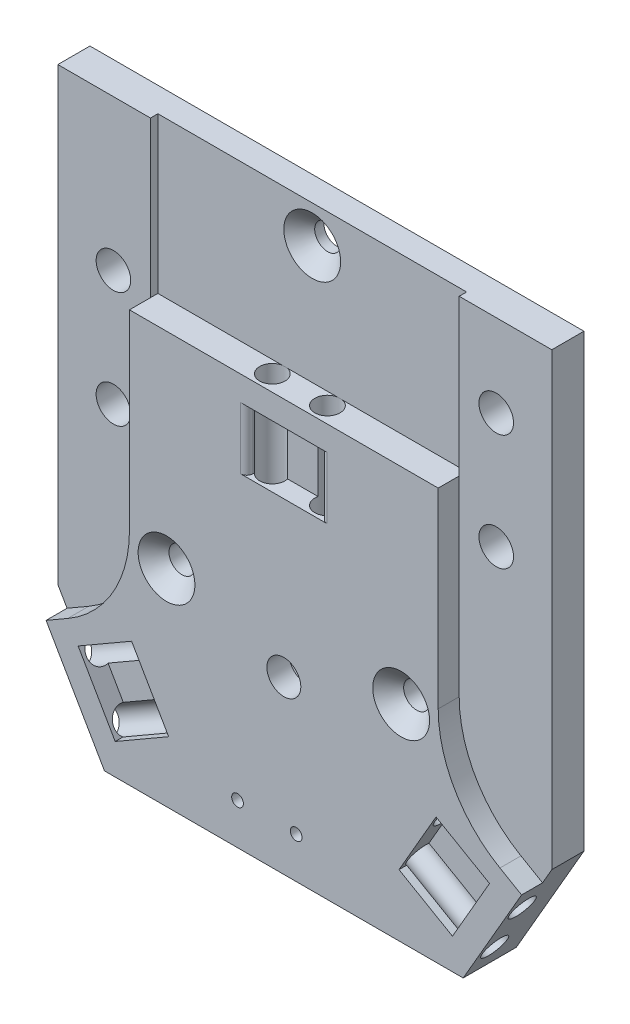
SolidWorks part; units mm, degrees
other "carriage coupler plate"
material "PET"
ref_plane "Front" through (0, 0, 0) normal (0, 0, 1) x (1, 0, 0)
ref_plane "Top" through (0, 0, 0) normal (0, 1, 0) x (1, 0, 0)
ref_plane "Right" through (0, 0, 0) normal (1, 0, 0) x (0, 0, -1)
sketch "Sketch1" plane through (0, 0, 0) normal (0, 0, 1) x (1, 0, 0)
  line L0 (0, 0) -> (0, 30) construction
  line L1 (0, 0) -> (25.9808, -15) construction
  line L2 (0, 0) -> (-25.9808, -15) construction
  dimension "D1" = 120
  dimension "D2" = 120
  dimension "D3" = 30
ref_plane "Plane1" through (0, 30, 0) normal (0, 1, 0) x (1, 0, 0)
sketch "Sketch2" plane through (0, 30, 0) normal (0, 1, 0) x (1, 0, 0)
  line L0 (-4.4589, 0) -> (0, -4.0148) construction
  line L1 (0, 0) -> (-25.9808, 0) construction
  line L2 (0, 0) -> (0, -4.0148) construction
  line L3 (-4.4589, 0) -> (0, 0) construction
  line L4 (0, -5.3962) -> (0, -4.0148) construction
  line L5 (0, -5.3962) -> (-4.4589, 0) construction
  line L7 (-4, -4.0148) -> (4, -4.0148) construction
  line L8 (3.9519, -3.3962) -> (-3.9519, -3.3962) construction
  line L9 (0, -0.3962) -> (0, -3.3962) construction
  line L10 (0, -4.0148) -> (0, -7.3926) construction
  circle A0 centre (-4.4589, 0) radius 2
  circle A1 centre (4.4589, 0) radius 2
  circle A2 centre (0, -4.0148) radius 4
  circle A3 centre (0, -5.3962) radius 5 construction
  circle A4 centre (0, -7.3926) radius 1.5
  dimension "D1" = 4
  dimension "D2" = 8
  dimension "D4" = 10
  dimension "D9" = 3
  dimension "D6" = 7.3926
  dimension "D8" = 8.9177
  dimension "D3" = 42
  dimension "D5" = 50.433
  dimension "D7" = 3.3962
  dimension "D10" = 0.6186
sketch "Sketch3" plane through (0, 0, 0) normal (0, 0, 1) x (1, 0, 0)
  line L0 (0, 30) -> (0, 35) construction
  line L2 (0, 35) -> (0, 39) construction
  line L3 (-25, 39) -> (25, 39)
  line L4 (25, 39) -> (25, -3.5116)
  line L5 (25, -3.5116) -> (38.5044, -11.3084)
  line L6 (0, 0) -> (0, 30) construction
  line L7 (-25, -3.5116) -> (-38.5044, -11.3084)
  line L8 (-25, 39) -> (-25, -3.5116)
  line L9 (4.4589, 30) -> (4.4589, 39) construction
  line L10 (25.9808, -15) -> (33.775, -19.5) construction
  line L11 (29.0456, -27.6916) -> (-29.0456, -27.6916)
  line L13 (0, 0) -> (25.9808, -15) construction
  line L14 (33.775, -19.5) -> (38.5044, -11.3084)
  line L15 (4.4589, 30) -> (0, 30) construction
  line L16 (4.4589, 30) -> (9.4589, 30) construction
  line L17 (-33.775, -19.5) -> (-38.5044, -11.3084)
  line L18 (33.775, -19.5) -> (29.0456, -27.6916)
  line L19 (-33.775, -19.5) -> (-29.0456, -27.6916)
  dimension "D1" = 5
  dimension "D2" = 4
  dimension "D3" = 25
  dimension "D4" = 120
  dimension "D5" = 5
  dimension "D6" = 9.4589
  dimension "D7" = 9.4589
  dimension "D8" = 9
  dimension "D9" = 9
extrude "Boss-Extrude1" add sketch "Sketch3" along normal blind 2.6 and the other way blind 6
fillet "Fillet1" radius 20 2 edges at (-25, -3.5116, -1.7) (25, -3.5116, -1.7)
sketch "Sketch4" plane through (0, 30, 0) normal (0, 1, 0) x (1, 0, 0)
  line L0 (0, -0.0148) -> (0, 0.4852) construction
  line L1 (5.1148, 0.4852) -> (-5.1148, 0.4852)
  line L2 (-5.1148, 0.4852) -> (-6, -0.4)
  line L3 (-6, -0.4) -> (-6, -2.6)
  line L4 (25, -2.6) -> (-25, -2.6) construction
  line L5 (-6, -2.6) -> (6, -2.6)
  line L7 (0, -5.3962) -> (-4.4589, 0) construction
  line L8 (-0.7342, -4.5076) -> (-0.5833, -4.3426)
  line L9 (6, -0.4) -> (6, -2.6)
  line L10 (5.1148, 0.4852) -> (6, -0.4)
  circle A7 centre (0, -4.0148) radius 4 construction
  dimension "D1" = 0.5
  dimension "D2" = 135
  dimension "D3" = 12
  dimension "D4" = 2.2
extrude "Cut-Extrude1" cut sketch "Sketch4" against normal blind 5 and the other way blind 5 contours L5 L9 L10 L1 L2 L3
sketch "Sketch5" plane through (0, 39, 0) normal (0, 1, 0) x (1, 0, 0)
  circle A2 centre (-4.4589, 0) radius 2.05
  circle A3 centre (4.4589, 0) radius 2.05
  dimension "D1" = 4.1
  dimension "D2" = 4.1
extrude "Cut-Extrude2" cut sketch "Sketch5" against normal blind 20
fillet "Fillet3" radius 1 2 edges at (-6, 30, 2.6) (6, 30, 2.6)
ref_axis "Axis1" through (0, 0, -80.9) along (0, 0, 1)
pattern_circular "CirPattern1" count 3 over 360 about axis through (0, 0, -80.9) along (0, 0, 1) of "Cut-Extrude2", "Cut-Extrude1"
sketch "Sketch6" plane through (0, 0, 2.6) normal (0, 0, 1) x (1, 0, 0)
  circle A0 centre (0, 0) radius 2.75
  dimension "D1" = 5.5
extrude "Cut-Extrude3" cut sketch "Sketch6" against normal through all
sketch "Sketch7" plane through (0, 0, -6) normal (0, 0, -1) x (-1, 0, 0)
  line L2 (0, 0) -> (0, 58.2) construction
  line L3 (-25, 39) -> (25, 39) construction
  line L4 (-25, 39) -> (25, 39)
  line L5 (-25, 39) -> (-25, 54)
  line L6 (-25, 54) -> (-2.3663, 63.7137)
  line L7 (25, 39) -> (25, 54)
  line L8 (25, 54) -> (2.3663, 63.7137)
  arc A0 (2.3663, 63.7137) -> (-2.3663, 63.7137) centre (0, 58.2) ccw
  dimension "D1" = 12
  dimension "D2" = 19.2
  dimension "D3" = 15
extrude "Boss-Extrude2" add sketch "Sketch7" against normal blind 4
sketch "Sketch8" plane through (0, 0, 2.6) normal (0, 0, 1) x (1, 0, 0)
  line L0 (0, 0) -> (0, 58.2) construction
  line L1 (-19, 5.7) -> (19, 5.7) construction
  circle A0 centre (-19, 5.7) radius 2.1
  circle A1 centre (19, 5.7) radius 2.1
  circle A2 centre (0, 58.2) radius 2.1
  arc A3 (2.3663, 63.7137) -> (-2.3663, 63.7137) centre (0, 58.2) ccw construction
  point P10 (0, 5.7)
  dimension "D1" = 4.2
  dimension "D2" = 4.2
  dimension "D3" = 4.2
  dimension "D4" = 52.5
  dimension "D5" = 38
extrude "Cut-Extrude4" cut sketch "Sketch8" against normal through all
chamfer "Chamfer1" distance 2.5 angle 45 3 edges at (-16.9, 5.7, 2.6) (21.1, 5.7, 2.6) (-2.1, 58.2, -2)
sketch "Sketch9" plane through (0, 0, -6) normal (0, 0, -1) x (-1, 0, 0)
  line L0 (0, -27.6916) -> (0, -6.1064) construction
  line L1 (29.0456, -27.6916) -> (-29.0456, -27.6916) construction
  line L2 (-2, -21.0416) -> (7.5, -21.0416) construction
  circle A0 centre (7.5, -21.0416) radius 0.95
  circle A1 centre (-2, -21.0416) radius 0.95
  dimension "D4" = 1.9
  dimension "D5" = 1.9
  dimension "D1" = 6.65
  dimension "D2" = 7.5
  dimension "D3" = 9.5
extrude "Cut-Extrude5" cut sketch "Sketch9" against normal through all
sketch "Sketch10" plane through (0, 0, -6) normal (0, 0, -1) x (-1, 0, 0)
  line L0 (25, 54) -> (38.5044, 48.2043)
  line L2 (25, 8.0354) -> (25, 54)
  line L4 (38.5044, -11.3084) -> (38.5044, 48.2043)
  line L7 (38.5044, -11.3084) -> (38.5044, 22.7) construction
  line L8 (35, -9.2851) -> (38.5044, -11.3084)
  line L9 (25, 54) -> (2.3663, 63.7137) construction
  arc A2 (35, -9.2851) -> (25, 8.0354) centre (45, 8.0354) cw
extrude "Boss-Extrude3" add sketch "Sketch10" against normal blind 5.2
sketch "Sketch11" plane through (0, 0, -6) normal (0, 0, -1) x (-1, 0, 0)
  line L0 (-38.5044, -11.3084) -> (-38.5044, 64.2)
  line L2 (-38.5044, -11.3084) -> (-35, -9.2851)
  line L3 (-25, 8.0354) -> (-25, 54)
  line L7 (0, 64.2) -> (-38.5044, 64.2)
  line L8 (-25, 54) -> (-2.3663, 63.7137)
  line L9 (-2.3663, 63.7137) -> (-25, 54) construction
  arc A2 (-35, -9.2851) -> (-25, 8.0354) centre (-45, 8.0354) ccw
  arc A4 (2.3663, 63.7137) -> (-2.3663, 63.7137) centre (0, 58.2) ccw construction
  arc A5 (-2.3663, 63.7137) -> (0, 64.2) centre (0, 58.2) cw
extrude "Boss-Extrude4" add sketch "Sketch11" against normal blind 5.2
sketch "Sketch12" plane through (0, 0, -0.8) normal (0, 0, 1) x (1, 0, 0)
  line L0 (-38.5044, 39.8275) -> (-31, 39.8275) construction
  line L1 (-38.5044, -11.3084) -> (-38.5044, 48.2043) construction
  line L2 (38.5044, 50.8275) -> (31, 50.8275) construction
  line L3 (38.5044, 64.2) -> (38.5044, -11.3084) construction
  line L4 (25, 8.0354) -> (25, 39) construction
  line L5 (-25, 39) -> (-25, 8.0354) construction
  line L6 (25, 39) -> (-25, 39) construction
  line L7 (-31, 39.8275) -> (-31, 21.0775) construction
  line L8 (25, 39) -> (4.9089, 39) construction
  line L9 (31, 50.8275) -> (31, 32.0775) construction
  circle A0 centre (-31, 39.8275) radius 2.8
  circle A1 centre (31, 50.8275) radius 2.8
  circle A2 centre (-31, 21.0775) radius 2.8
  circle A3 centre (31, 32.0775) radius 2.8
  dimension "D5" = 5.6
  dimension "D6" = 5.6
  dimension "D7" = 5.6
  dimension "D9" = 5.6
  dimension "D1" = 0.8275
  dimension "D2" = 11.8275
  dimension "D3" = 6
  dimension "D4" = 6
  dimension "D8" = 18.75
  dimension "D10" = 18.75
fillet "Fillet4" radius 10 1 edges at (38.5044, 64.2, -3.4)
sketch "Sketch13" plane through (0, 0, -6) normal (0, 0, -1) x (-1, 0, 0)
  circle A0 centre (0, 0) radius 7
  dimension "D1" = 14
extrude "Cut-Extrude7" cut sketch "Sketch13" against normal blind 5
sketch "Sketch14" plane through (0, 0, -0.8) normal (0, 0, 1) x (1, 0, 0)
  line L0 (0, 64.2) -> (28.5044, 64.2) construction
  line L1 (-25, 39) -> (25, 39)
  line L2 (-25, 39) -> (-25, 64.2)
  line L3 (-25, 64.2) -> (25, 64.2)
  line L4 (25, 39) -> (25, 64.2)
  line L5 (25, 8.0354) -> (25, 39) construction
extrude "Cut-Extrude8" cut sketch "Sketch14" against normal up to surface (1.2 mm away) up to face at (-4.6, 58.2, -2)
hole_wizard "Ø5.6 (5.6) Diameter Hole1" positions "Sketch15" profile "Sketch16" hole size "Ø5.6" standard "ANSI Metric" end condition through all
sketch "Sketch15" plane through (0, 0, -0.8) normal (0, 0, 1) x (1, 0, 0)
  point P0 (-31, 39.8275)
  point P3 (-31, 21.0775)
  point P6 (31, 32.0775)
  point P9 (31, 50.8275)
sketch "Sketch16" plane through (-31, 39.8275, -0.8) normal (1, 0, 0) x (0, -1, 0)
  line L0 (0, 0) -> (0, 5.2)
  line L1 (0, 5.2) -> (2.8, 5.2)
  line L2 (2.8, 5.2) -> (2.8, 0)
  line L5 (2.8, 0) -> (0, 0)
  line L11 (0, -6.35) -> (0, 107.95) construction
  dimension "Thru Hole Dia." = 5.6
  dimension "Thru Hole Depth" = 5.2
sketch "Sketch17" plane through (0, 0, -6) normal (0, 0, -1) x (-1, 0, 0)
  line L0 (-38.5044, -11.3084) -> (-40, -8.718)
  line L1 (-40, -8.718) -> (-40, 64.2)
  line L2 (-40, 64.2) -> (-28.5044, 64.2)
  line L3 (-29.0456, -27.6916) -> (-38.5044, -11.3084) construction
  line L4 (-38.5044, 54.2) -> (-38.5044, -11.3084)
  line L5 (38.5044, -11.3084) -> (40, -8.718)
  line L6 (40, -8.718) -> (40, 64.2)
  line L7 (40, 64.2) -> (0, 64.2)
  line L9 (38.5044, -11.3084) -> (38.5044, 48.2043)
  line L12 (38.5044, 48.2043) -> (2.3663, 63.7137)
  circle A0 centre (0, 0) radius 2.75 construction
  arc A1 (-28.5044, 64.2) -> (-38.5044, 54.2) centre (-28.5044, 54.2) ccw
  arc A2 (-28.5044, 64.2) -> (-38.5044, 54.2) centre (-28.5044, 54.2) ccw construction
  arc A3 (0, 64.2) -> (2.3663, 63.7137) centre (-1.7944, 49.4688) cw
  dimension "D1" = 40
  dimension "40" = 40
extrude "Boss-Extrude5" add sketch "Sketch17" against normal up to surface (5.2 mm away) up to face at (-28.2, 39.8275, -0.8)
sketch "Sketch18" plane through (0, 0, -2) normal (0, 0, 1) x (1, 0, 0)
  line L1 (-25, 39) -> (25, 39)
  line L2 (-25, 39) -> (-25, 64.2)
  line L3 (-25, 64.2) -> (25, 64.2)
  line L4 (25, 39) -> (25, 64.2)
extrude "Cut-Extrude9" cut sketch "Sketch18" along normal blind 10
